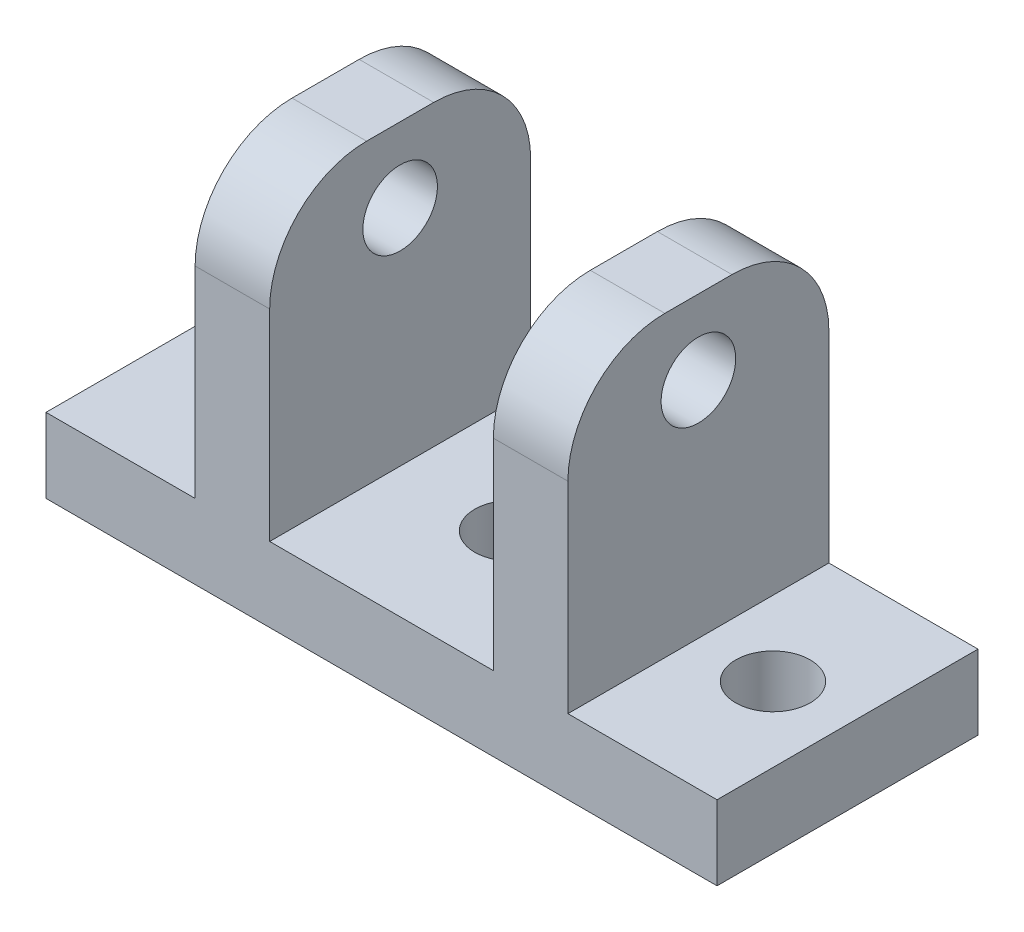
SolidWorks part; units mm, degrees
material "6061-T6 (SS)"
ref_plane "Front Plane" through (0, 0, 0) normal (0, 0, 1) x (1, 0, 0)
ref_plane "Top Plane" through (0, 0, 0) normal (0, 1, 0) x (1, 0, 0)
ref_plane "Right Plane" through (0, 0, 0) normal (1, 0, 0) x (0, 0, -1)
sketch "Sketch2" plane through (0, 0, 0) normal (0, 1, 0) x (1, 0, 0)
  line L0 (12.7, 22.225) -> (12.7, 0)
  line L1 (0, 0) -> (57.15, 0)
  line L2 (0, 0) -> (0, 22.225)
  line L3 (0, 22.225) -> (57.15, 22.225)
  line L4 (57.15, 0) -> (57.15, 22.225)
  line L5 (19.05, 22.225) -> (19.05, 0)
  line L6 (38.1, 22.225) -> (38.1, 0)
  line L7 (44.45, 22.225) -> (44.45, 0)
  dimension "D1" = 57.15
  dimension "D2" = 22.225
  dimension "D3" = 12.7
  dimension "D4" = 6.35
  dimension "D5" = 12.7
  dimension "D6" = 6.35
extrude "Boss-Extrude1" add sketch "Sketch2" along normal blind 6.35 contours L3 L2 L1 L0 | L3 L7 L1 L4 | L6 L3 L5 L1 region at (6.35, 0, -11.1125) region at (28.575, 0, -11.1125) region at (50.8, 0, -11.1125)
extrude "Boss-Extrude2" add sketch "Sketch2<3>" along normal blind 31.75 contours L5 L3 L0 L1 | L7 L3 L6 L1 region at (15.875, 0, -11.1125) region at (41.275, 0, -11.1125)
sketch "Sketch2<3>" plane through (0, 0, 0) normal (0, 1, 0) x (1, 0, 0) same geometry as "Sketch2"
sketch "Sketch3" plane through (12.7, 0, 0) normal (-1, 0, 0) x (0, 0, 1)
  line L0 (-22.225, 6.35) -> (-6.35, 6.35)
  line L1 (-22.225, 6.35) -> (0, 6.35) construction
  line L3 (-22.225, 31.75) -> (0, 31.75) construction
  line L4 (-22.225, 6.35) -> (0, 6.35)
  line L5 (-22.225, 6.35) -> (-22.225, 31.75)
  line L6 (-22.225, 31.75) -> (0, 31.75)
  line L7 (0, 6.35) -> (0, 31.75)
  line L8 (-11.1125, 31.75) -> (-11.1125, 25.4) construction
  circle A0 centre (-11.1125, 25.4) radius 3.175
  dimension "D5" = 6.35
  dimension "D2" = 6.35
  dimension "D3" = 22.225
  dimension "D4" = 6.35
extrude "Cut-Extrude1" cut sketch "Sketch3" against normal through all contours A0 region at (12.7, 25.4, -11.1125)
sketch "Sketch4" plane through (0, 6.35, 0) normal (0, 1, 0) x (1, 0, 0)
  line L0 (0, 11.1125) -> (57.15, 11.1125) construction
  line L1 (0, 0) -> (0, 22.225) construction
  line L2 (57.15, 0) -> (57.15, 22.225) construction
  circle A0 centre (6.35, 11.1125) radius 6.35
  circle A1 centre (28.575, 11.1125) radius 6.35
  circle A2 centre (50.8, 11.1125) radius 6.35
  dimension "D1" = 12.7
  dimension "D2" = 12.7
  dimension "D3" = 12.7
hole_wizard "1/4 (0.25) Diameter Hole1" positions "3DSketch1" profile "Sketch5" hole size "1/4" standard "ANSI Inch"
sketch3d "3DSketch1"
  point P0 (6.35, 6.35, -11.1125)
  point P3 (28.575, 6.35, -11.1125)
  point P6 (50.8, 6.35, -11.1125)
sketch "Sketch5" plane through (6.35, 6.35, -11.1125) normal (1, 0, 0) x (0, 0, 1)
  line L0 (0, 0) -> (0, 27.3077)
  line L1 (0, 27.3077) -> (3.175, 25.4)
  line L2 (3.175, 25.4) -> (3.175, 0)
  line L5 (3.175, 0) -> (0, 0)
  line L10 (0, 27.3077) -> (-3.175, 25.4) construction
  line L11 (0, -6.35) -> (0, 107.95) construction
  dimension "Hole Dia." = 6.35
  dimension "Hole Depth" = 25.4
  dimension "Drill Angle" = 118
fillet "Fillet1" radius 8.255 4 edges at (15.875, 31.75, -22.225) (41.275, 31.75, -22.225) (41.275, 31.75, 0) (15.875, 31.75, 0)
